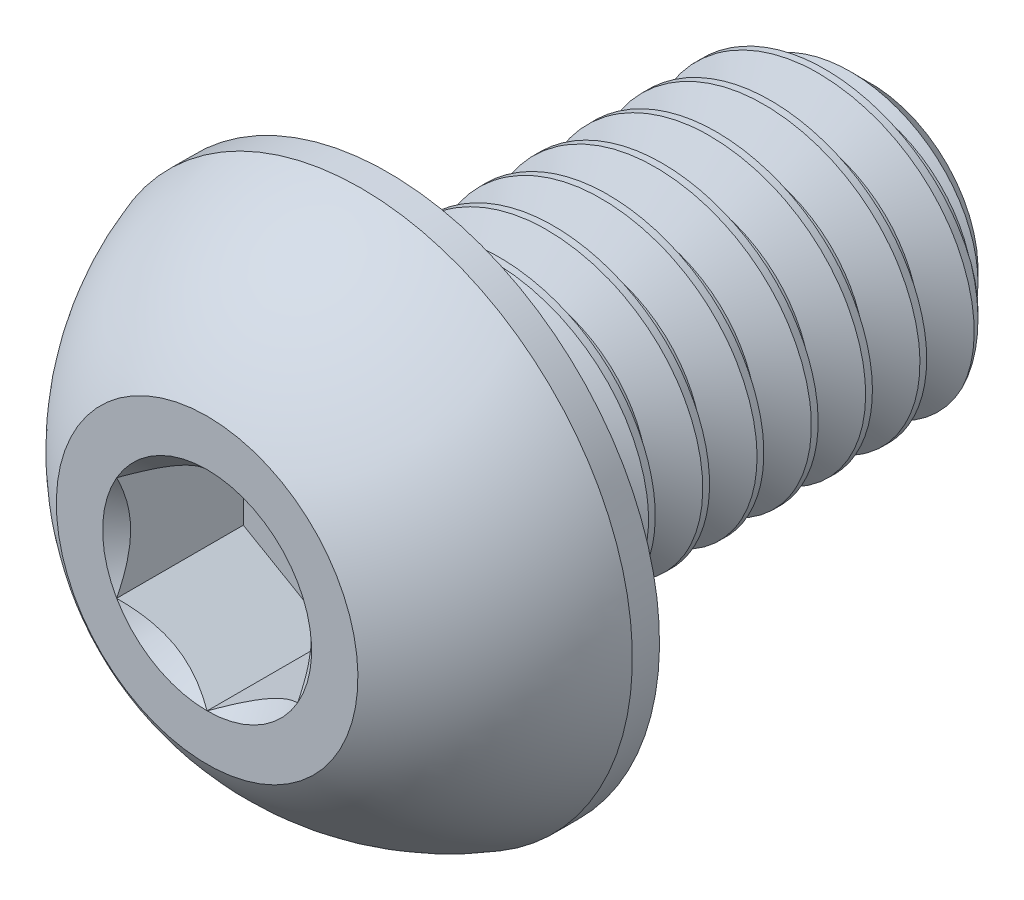
SolidWorks part; units mm, degrees
ref_plane "Front Plane" through (0, 0, 0) normal (0, 0, 1) x (1, 0, 0)
ref_plane "Top Plane" through (0, 0, 0) normal (0, 1, 0) x (1, 0, 0)
ref_plane "Right Plane" through (0, 0, 0) normal (1, 0, 0) x (0, 0, -1)
sketch "Sketch1" plane through (0, 0, 0) normal (1, 0, 0) x (0, 0, -1)
  line L0 (-2.75, 0) -> (2.75, 0) construction
  line L1 (-1.25, 2.25) -> (-1.25, -2.25) construction
  line L2 (2.75, 1.25) -> (2.75, -1.25) construction
  line L3 (2.7219, 1.2987) -> (2.9469, 0.909) construction
  line L4 (2.9469, 0.909) -> (3.1719, 1.2987) construction
  line L5 (3.1719, 1.2987) -> (2.7219, 1.2987) construction
  line L6 (2.75, 1.25) -> (3.1437, 1.25) construction
  line L7 (2.9469, 1.2987) -> (2.9469, 1.25) construction
  line L8 (2.9469, 1.25) -> (2.9469, 0.9577) construction
  line L9 (2.9469, 0.9577) -> (2.9469, 0.909) construction
  line L10 (2.9187, 0.9577) -> (2.975, 0.9577)
  line L11 (2.7359, 1.2744) -> (3.1578, 1.2744)
  line L12 (2.975, 0.9577) -> (3.1578, 1.2744)
  line L13 (2.9187, 0.9577) -> (2.7359, 1.2744)
  line L14 (-2.75, 0.75) -> (-2.75, -0.75) construction
  line L15 (2.75, 1.25) -> (-1.25, 1.25) construction
  point P3 (-1.25, 0)
  point P6 (-1.7, 0)
  point P21 (2.9469, 1.2744)
  point P24 (-1.475, 2.25)
  point P25 (1.625, -1.25)
  point P26 (-2.75, 1.25)
  dimension "Head Height" = 1.5
  dimension "Length" = 4
  dimension "Head Dia" = 4.5
  dimension "Thread Dia" = 2.5
  dimension "Pitch" = 0.45
  dimension "D2" = 0.0563
  dimension "Drive Size" = 1.5
  dimension "D1" = 1.05
  dimension "D3" = 0.225
  dimension "D4" = 1.125
sketch "Sketch2" plane through (0, 0, 0) normal (1, 0, 0) x (0, 0, -1)
  line L0 (-2.75, 0) -> (2.75, 0)
  line L1 (2.75, 0) -> (2.75, 0.89)
  line L2 (2.75, 1.25) -> (2.75, -1.25) construction
  line L3 (2.75, 0.89) -> (2.39, 1.25)
  line L4 (2.39, 1.25) -> (-1.25, 1.25)
  line L5 (-1.25, 2.25) -> (-1.25, -2.25) construction
  line L6 (-1.25, 1.25) -> (-1.25, 2.25)
  line L7 (-1.25, 2.25) -> (-1.475, 2.25)
  line L8 (2.75, 1.25) -> (3.1437, 1.25) construction
  line L9 (-2.75, 0) -> (-2.75, 1.25)
  arc A0 (-2.75, 1.25) -> (-1.475, 2.25) centre (-0.74, 0) cw
  dimension "D1" = 0.36
  dimension "D2" = 45
revolve "Revolve1" add sketch "Sketch2" angle 360 about L0
sketch "Sketch3" plane through (0, 0, 2.75) normal (0, 0, 1) x (1, 0, 0)
  line L1 (0, 0.866) -> (-0.75, 0.433)
  line L2 (-0.75, 0.433) -> (-0.75, -0.433)
  line L3 (-0.75, -0.433) -> (0, -0.866)
  line L4 (0, -0.866) -> (0.75, -0.433)
  line L5 (0.75, -0.433) -> (0.75, 0.433)
  line L6 (0.75, 0.433) -> (0, 0.866)
  circle A0 centre (0, 0) radius 0.75 construction
  dimension "D1" = 1.5
extrude "Cut-Extrude1" cut sketch "Sketch3" against normal up to vertex (1.05 mm away) up to point (0, 0, 1.7)
sketch "Sketch4" plane through (0, 0, 2.75) normal (0, 0, 1) x (1, 0, 0)
  circle A0 centre (0, 0) radius 0.866
extrude "Cut-Extrude2" cut sketch "Sketch4" against normal blind 10 draft 45
split "Split1" bodies to split 106 resulting bodies 107 108 split by face at (0, -2.25, 1.25)
sketch "Sketch5" plane through (0, 0, -2.75) normal (0, 0, -1) x (-1, 0, 0)
  circle A0 centre (0, 0) radius 1.25 construction
  circle A1 centre (0, 0) radius 1.25
curve "Helix/Spiral1" pitch 0.45 height 4.45 radius 1.25 centre (0, 0, -2.75) axis (0, 0, 1) start towards (0, 1, 0)
sketch "Sketch6" plane through (0, 0, 0) normal (1, 0, 0) x (0, 0, -1)
  line L0 (2.9187, 0.9577) -> (2.975, 0.9577) construction
  line L1 (2.9187, 0.9577) -> (2.7359, 1.2744) construction
  line L2 (2.7359, 1.2744) -> (3.1578, 1.2744) construction
  line L3 (2.975, 0.9577) -> (3.1578, 1.2744) construction
  line L4 (2.9187, 0.9577) -> (2.975, 0.9577)
  line L5 (2.9187, 0.9577) -> (2.7359, 1.2744)
  line L6 (2.7359, 1.2744) -> (3.1578, 1.2744)
  line L7 (2.975, 0.9577) -> (3.1578, 1.2744)
sweep "Cut-Sweep1" cut profiles "Sketch6" path "Helix/Spiral1" align with end faces yes
sketch "Sketch7" plane through (0, 0, 1.25) normal (0, 0, -1) x (-1, 0, 0)
  circle A1 centre (0, 0) radius 1.25
  circle A2 centre (0, 0) radius 1.25
  dimension "D1" = 0
extrude "Boss-Extrude1" add sketch "Sketch7" along normal blind 10 draft 30
equation "\"D2@Sketch1\" = \"Pitch@Sketch1\" / 8"
equation "\"D1@Sketch1\"=\"Drive Size@Sketch1\"*.7"
equation "\"D3@Sketch1\"=\"Head Height@Sketch1\"*.15"
equation "\"D1@Sketch2\"=\"Pitch@Sketch1\"*.8"
equation "\"D1@Sketch3\"=\"Drive Size@Sketch1\""
equation "\"D4@Helix/Spiral1\"=\"Pitch@Sketch1\""
equation "\"D3@Helix/Spiral1\"=\"Length@Sketch1\"+\"Pitch@Sketch1\""
equation "\"D4@Sketch1\"=\"Pitch@Sketch1\"*2.5"
